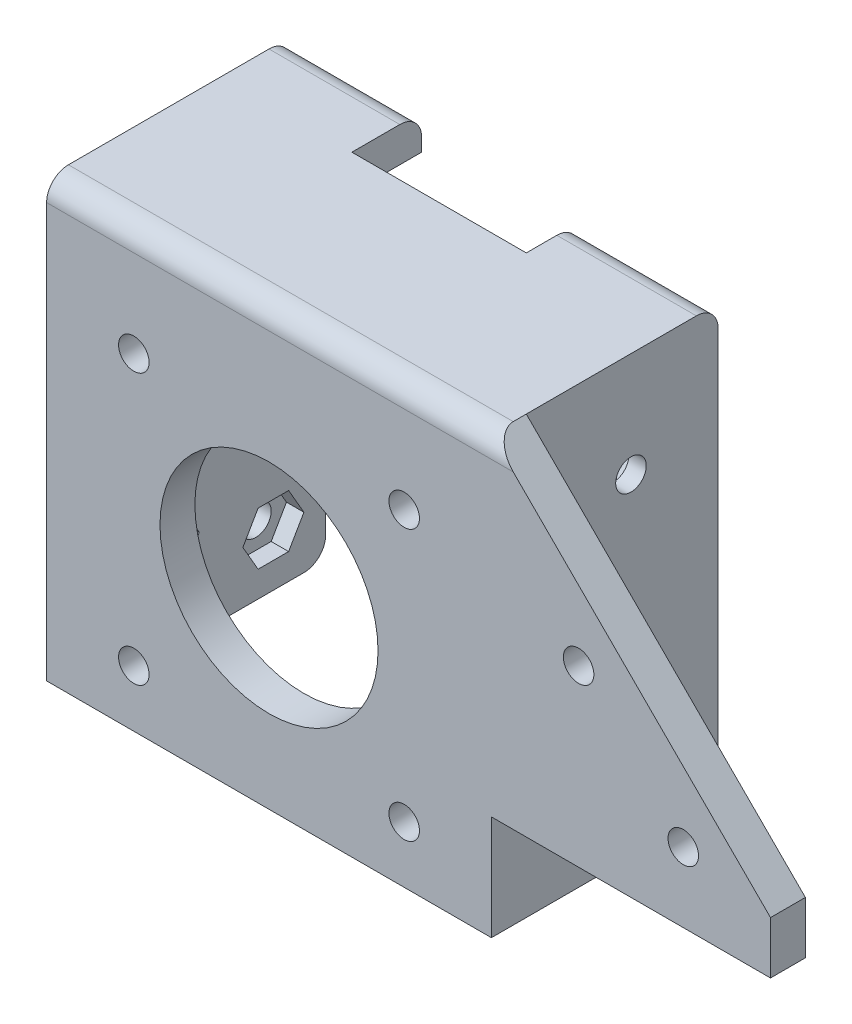
SolidWorks part; units mm, degrees
ref_plane "Front Plane" through (0, 0, 0) normal (0, 0, 1) x (1, 0, 0)
ref_plane "Top Plane" through (0, 0, 0) normal (0, 1, 0) x (1, 0, 0)
ref_plane "Right Plane" through (0, 0, 0) normal (1, 0, 0) x (0, 0, -1)
sketch "Sketch1" plane through (0, 0, 0) normal (0, 0, 1) x (1, 0, 0)
  line L0 (-50.3416, 0) -> (46.1674, 0) construction
  line L1 (0, -28.4394) -> (0, 79.8206) construction
  line L2 (57.5, 18) -> (25.5, 50)
  line L4 (-25.5, 0) -> (-25.5, 50)
  line L5 (-25.5, 50) -> (25.5, 50)
  line L6 (57.5, 12) -> (57.5, 18)
  line L7 (25.5, -2.2452) -> (25.5, 66.7313) construction
  line L10 (57.5, 12) -> (25.5, 12)
  line L11 (25.5, 12) -> (25.5, 0)
  line L12 (25.5, 0) -> (-25.5, 0)
  dimension "D1" = 50
  dimension "D2" = 38
  dimension "D3" = 6
  dimension "D5" = 25.5
  dimension "D6" = 45
  dimension "D7" = 51
extrude "Boss-Extrude1" add sketch "Sketch1" along normal blind 4
sketch "Sketch2" plane through (0, 0, 4) normal (0, 0, 1) x (1, 0, 0)
  line L0 (-39.1184, 22) -> (53.5, 22) construction
  line L1 (0, -8.7046) -> (0, 47.1631) construction
  line L2 (57.5, 18) -> (25.5, 50) construction
  line L3 (-15.5, 6.5) -> (15.5, 6.5) construction
  line L4 (-15.5, 6.5) -> (-15.5, 37.5) construction
  line L5 (-15.5, 37.5) -> (15.5, 37.5) construction
  line L6 (15.5, 6.5) -> (15.5, 37.5) construction
  line L7 (-15.5, 6.5) -> (15.5, 37.5) construction
  line L8 (-15.5, 37.5) -> (15.5, 6.5) construction
  line L9 (-25.5, 0) -> (25.5, 0) construction
  circle A0 centre (0, 22) radius 12.5
  circle A1 centre (15.5, 6.5) radius 1.75
  circle A2 centre (15.5, 37.5) radius 1.75
  circle A3 centre (-15.5, 37.5) radius 1.75
  circle A4 centre (-15.5, 6.5) radius 1.75
  point P4 (0, 22)
  dimension "D1" = 3.5
  dimension "D4" = 25
  dimension "D2" = 31
  dimension "D3" = 22
extrude "Cut-Extrude1" cut sketch "Sketch2" against normal through all
sketch "Sketch9" plane through (0, 0, 0) normal (0, 0, -1) x (-1, 0, 0)
  line L0 (-61, 20) -> (-35.5, 20) construction
  line L1 (-35.5, 20) -> (-35.5, 48.0747) construction
  line L2 (-25.5, -5.4794) -> (-25.5, 53.2688) construction
  line L3 (-25.5, 12) -> (-57.5, 12) construction
  circle A1 centre (-47.5, 20) radius 1.75
  circle A2 centre (-35.5, 32) radius 1.75
  dimension "D5" = 3.5
  dimension "D1" = 12
  dimension "D3" = 12
  dimension "D4" = 8
  dimension "D2" = 10
extrude "Cut-Extrude2" cut sketch "Sketch9" against normal blind 4
sketch "Sketch13" plane through (0, 0, 4) normal (0, 0, 1) x (1, 0, 0)
  line L8 (-25.5, 34.0255) -> (-45.5, 34.0255)
  line L9 (-25.5, 50) -> (-25.5, 0) construction
  line L10 (-45.5, 34.0255) -> (-45.5, 96.6007)
  line L11 (-45.5, 96.6007) -> (-32.0913, 96.6007)
  line L13 (57.5, 18) -> (25.5, 50) construction
  line L14 (25.5, 50) -> (19.5, 56)
  line L15 (-25.5, 34.0255) -> (-25.5, 50)
  line L17 (-32.0913, 96.6007) -> (-32.0913, 74.4017)
  line L20 (19.5, 56) -> (-3.8448, 56)
  line L21 (25.5, 50) -> (-25.5, 50)
  arc A3 (-3.8448, 56) -> (-32.0913, 74.4017) centre (-11.974, 74.4017) cw
  dimension "D1" = 20
  dimension "D2" = 6
extrude "Boss-Extrude7" [suppressed] add sketch "Sketch13" against normal blind 4
sketch "Sketch16" [suppressed] plane through (0, 0, 4) normal (0, 0, 1) x (1, 0, 0)
  line L0 (-38.5457, 92.6569) -> (2.0281, 52.0832) construction
  line L1 (-45, 34.0255) -> (-25, 34.0255) construction
  line L2 (-38.5457, 96.6007) -> (-38.5457, 85.5222) construction
  line L3 (-32.0913, 96.6007) -> (-45, 96.6007) construction
  circle A0 centre (2.0281, 52.0832) radius 2
  circle A1 centre (-38.5457, 92.6569) radius 2
  dimension "D3" = 4
  dimension "D1" = 57.38
  dimension "D2" = 45
extrude "Cut-Extrude6" [suppressed] cut sketch "Sketch16" against normal blind 4
sketch "Sketch17" plane through (0, 0, 0) normal (0, 0, -1) x (-1, 0, 0)
  line L0 (-25.5, 0) -> (-25.5, 50)
  line L2 (-25.5, 50) -> (25.5, 50)
  line L3 (25.5, 50) -> (25.5, 0) construction
  line L4 (25.5, 50) -> (25.5, 0)
  line L5 (25.5, 0) -> (21.5, 0)
  line L6 (25.5, 0) -> (-25.5, 0) construction
  line L7 (21.5, 0) -> (21.5, 46)
  line L8 (21.5, 46) -> (-21.5, 46)
  line L9 (-21.5, 46) -> (-21.5, 0)
  line L10 (-21.5, 0) -> (-25.5, 0)
  dimension "D1" = 43
  dimension "D2" = 21.5
  dimension "D3" = 4
extrude "Boss-Extrude8" add sketch "Sketch17" along normal blind 24
sketch "Sketch18" plane through (25.5, 0, 0) normal (1, 0, 0) x (0, 0, -1)
  line L0 (12, 4.8734) -> (12, 63.3892) construction
  circle A0 centre (12, 38) radius 1.75
  circle A1 centre (12, 20) radius 1.75
  dimension "D1" = 3.5
  dimension "D2" = 20
  dimension "D3" = 18
  dimension "D4" = 12
extrude "Cut-Extrude7" cut sketch "Sketch18" against normal up to surface (4 mm away) up to face at (21.5, 23, -12)
sketch "Sketch19" plane through (-25.5, 0, 0) normal (-1, 0, 0) x (0, 0, 1)
  line L0 (-6, 10) -> (-6, 45) construction
  line L2 (4, 0) -> (-24, 0) construction
  line L4 (-18, 6) -> (-6, 6) construction
  line L5 (-18, 6) -> (-18, 41) construction
  line L6 (-18, 41) -> (-6, 41) construction
  line L7 (-6, 6) -> (-6, 41) construction
  circle A0 centre (-18, 6) radius 1.75
  circle A2 centre (-18, 41) radius 1.75
  circle A5 centre (-6, 10) radius 1.75
  circle A6 centre (-6, 45) radius 1.75
  dimension "D5" = 3.5
  dimension "D4" = 12
  dimension "D2" = 6
  dimension "D3" = 35
  dimension "D1" = 6
  dimension "D6" = 35
  dimension "D7" = 10
extrude "Cut-Extrude8" cut sketch "Sketch19" against normal blind 10
sketch "Sketch20" plane through (0, 50, 0) normal (0, 1, 0) x (1, 0, 0)
  line L0 (-25.5, 24) -> (25.5, 24) construction
  line L1 (25.5, 24) -> (-10.5, 24)
  line L2 (25.5, 24) -> (25.5, 22)
  line L4 (-10.5, 24) -> (-10.5, 16)
  line L6 (25.5, 24) -> (25.5, 0) construction
  line L7 (-10.5, 16) -> (9.5, 16)
  line L8 (9.5, 16) -> (9.5, 22)
  line L9 (9.5, 22) -> (25.5, 22)
  dimension "D1" = 20
  dimension "D2" = 2
  dimension "D3" = 16
  dimension "D4" = 6
extrude "Cut-Extrude9" cut sketch "Sketch20" against normal up to surface (50 mm away) up to face at (0, 0, -11)
fillet "Fillet1" radius 2.5 4 edges at (17.5, 50, -22) (-18, 50, -24) (23.5, 0, -22) (-23.5, 0, -24)
sketch "Sketch22" plane through (-21.5, 0, 0) normal (1, 0, 0) x (0, 0, -1)
  line L0 (21.5, 0) -> (0, 0) construction
  line L1 (7.75, 41.9689) -> (9.5, 45)
  line L2 (9.5, 45) -> (7.75, 48.0311)
  line L3 (7.75, 48.0311) -> (4.25, 48.0311)
  line L4 (4.25, 48.0311) -> (2.5, 45)
  line L5 (2.5, 45) -> (4.25, 41.9689)
  line L6 (4.25, 41.9689) -> (7.75, 41.9689)
  circle A0 centre (6, 45) radius 3.0311 construction
  point P0 (6, 45)
  dimension "D1" = 3.5
extrude "Cut-Extrude11" cut sketch "Sketch22" along normal blind 3 and the other way blind 2
sketch "Sketch23" plane through (-21.5, 0, 0) normal (1, 0, 0) x (0, 0, -1)
  line L0 (21.5, 0) -> (0, 0) construction
  line L1 (19.75, 37.9689) -> (21.5, 41)
  line L2 (21.5, 41) -> (19.75, 44.0311)
  line L3 (19.75, 44.0311) -> (16.25, 44.0311)
  line L4 (16.25, 44.0311) -> (14.5, 41)
  line L5 (14.5, 41) -> (16.25, 37.9689)
  line L6 (16.25, 37.9689) -> (19.75, 37.9689)
  line L7 (7.75, 6.9689) -> (9.5, 10)
  line L8 (9.5, 10) -> (7.75, 13.0311)
  line L9 (7.75, 13.0311) -> (4.25, 13.0311)
  line L10 (4.25, 13.0311) -> (2.5, 10)
  line L11 (2.5, 10) -> (4.25, 6.9689)
  line L12 (4.25, 6.9689) -> (7.75, 6.9689)
  line L13 (16.25, 2.9689) -> (19.75, 2.9689)
  line L14 (19.75, 2.9689) -> (21.5, 6)
  line L15 (21.5, 6) -> (19.75, 9.0311)
  line L16 (19.75, 9.0311) -> (16.25, 9.0311)
  line L17 (16.25, 9.0311) -> (14.5, 6)
  line L18 (14.5, 6) -> (16.25, 2.9689)
  circle A0 centre (18, 41) radius 3.0311 construction
  circle A1 centre (6, 10) radius 3.0311 construction
  circle A2 centre (18, 6) radius 3.0311 construction
  point P0 (18, 41)
  point P1 (18, 6)
  point P3 (6, 10)
  dimension "D1" = 3.5
extrude "Cut-Extrude12" cut sketch "Sketch23" against normal blind 2
sketch "Sketch24" plane through (21.5, 0, 0) normal (-1, 0, 0) x (0, 0, 1)
  line L0 (-19.5, 0) -> (0, 0) construction
  line L1 (-10.2403, 41.0479) -> (-13.7597, 41.0479)
  line L2 (-13.7597, 41.0479) -> (-15.5194, 38)
  line L3 (-15.5194, 38) -> (-13.7597, 34.9521)
  line L4 (-13.7597, 34.9521) -> (-10.2403, 34.9521)
  line L5 (-10.2403, 34.9521) -> (-8.4806, 38)
  line L6 (-8.4806, 38) -> (-10.2403, 41.0479)
  line L7 (-10.25, 23.0311) -> (-13.75, 23.0311)
  line L8 (-13.75, 23.0311) -> (-15.5, 20)
  line L9 (-15.5, 20) -> (-13.75, 16.9689)
  line L10 (-13.75, 16.9689) -> (-10.25, 16.9689)
  line L11 (-10.25, 16.9689) -> (-8.5, 20)
  line L12 (-8.5, 20) -> (-10.25, 23.0311)
  circle A0 centre (-12, 38) radius 3.0479 construction
  circle A1 centre (-12, 20) radius 3.0311 construction
  point P0 (-12, 38)
  point P1 (-12, 20)
  dimension "D1" = 3.5
extrude "Cut-Extrude13" cut sketch "Sketch24" against normal blind 2
fillet "Fillet2" radius 2.5 1 edges at (0, 50, 4)
equation "\"motor_plate_thickness\"=4"
equation "\"D1@Boss-Extrude1\"=\"motor_plate_thickness\""
equation "\"motor_hub_diameter\"=25"
equation "\"D4@Sketch2\"=\"motor_hub_diameter\""
equation "\"motor_mount_hole_od\"=3.5"
equation "\"D1@Sketch2\"=\"motor_mount_hole_od\""
equation "\"motor_mount_hole_spacing\"=31"
equation "\"D2@Sketch2\"=\"motor_mount_hole_spacing\""
equation "\"D5@Sketch9\"=\"motor_mount_hole_od\""
equation "\"D1@Sketch18\"=\"motor_mount_hole_od\""
equation "\"D5@Sketch19\"=\"motor_mount_hole_od\""
